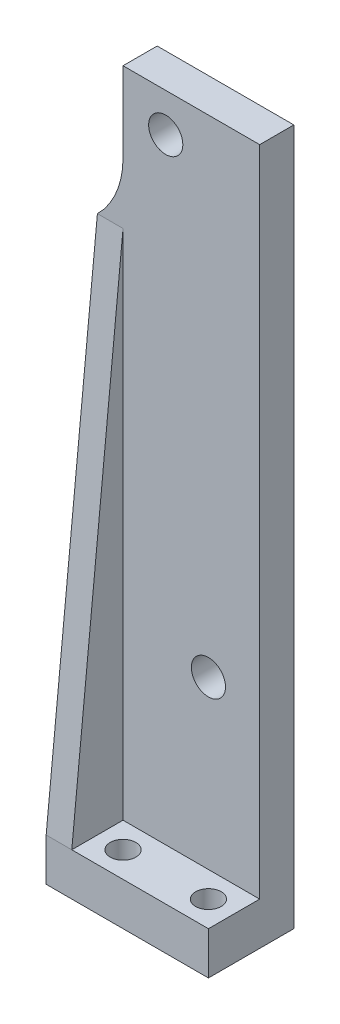
SolidWorks part; units mm, degrees
ref_plane "前视基准面" through (0, 0, 0) normal (0, 0, 1) x (1, 0, 0)
ref_plane "上视基准面" through (0, 0, 0) normal (0, 1, 0) x (1, 0, 0)
ref_plane "右视基准面" through (0, 0, 0) normal (1, 0, 0) x (0, 0, -1)
sketch "草图1" plane through (0, 0, 0) normal (0, 1, 0) x (1, 0, 0)
  line L0 (-10, 0) -> (-7, 0)
  line L1 (-10, 3) -> (6, 3)
  line L2 (-10, 3) -> (-10, -3)
  line L3 (-10, -3) -> (6, -3)
  line L4 (6, 3) -> (6, -3)
  line L5 (-10, 3) -> (6, -3) construction
  line L6 (-10, -3) -> (6, 3) construction
  line L7 (6, 0) -> (3, 0)
  circle A5 centre (-7, 0) radius 1.5
  circle A6 centre (3, 0) radius 1.5
extrude "凸台-拉伸1" add sketch "草图1" along normal blind 5 contours L7 L4 L1 L2 L0 | L0 L2 L3 L4 L7 region at (-2, 0, 0)
sketch "草图2" plane through (0, 0, -3) normal (0, 0, -1) x (-1, 0, 0)
  line L0 (-6, 0) -> (-6, 81.5)
  line L1 (-6, 81.5) -> (10, 81.5)
  line L2 (10, 81.5) -> (10, 0)
  line L3 (10, 0) -> (-6, 0)
extrude "凸台-拉伸2" add sketch "草图2" along normal blind 4 contours L0 L1 L2 L3
sketch "草图3" plane through (0, 0, -7) normal (0, 0, -1) x (-1, 0, 0)
  circle A0 centre (5, 77) radius 2
extrude "切除-拉伸1" cut sketch "草图3" against normal through all contours A0
sketch "草图4" plane through (0, 0, -7) normal (0, 0, -1) x (-1, 0, 0)
  line L0 (0, 0) -> (0, 24.5)
  circle A0 centre (0, 24.5) radius 2
extrude "切除-拉伸2" cut sketch "草图4" against normal through all contours A0
sketch "草图5" plane through (0, 0, -7) normal (0, 0, -1) x (-1, 0, 0)
  circle A0 centre (5, 77) radius 3.5
extrude "切除-拉伸3" cut sketch "草图5" against normal blind 1
sketch "草图6" plane through (-10, 0, 0) normal (-1, 0, 0) x (0, 0, 1)
  line L0 (-3, 5) -> (-3, 65)
  line L1 (-3, 81.5) -> (-3, 5) construction
  line L2 (-3, 65) -> (-7, 65)
  line L3 (-7, 81.5) -> (-7, 0) construction
  line L4 (-7, 65) -> (-7, 0)
  line L5 (-7, 0) -> (3, 0)
  line L6 (3, 0) -> (3, 5)
  line L7 (3, 5) -> (-3, 65)
  line M1 (-7, 0) -> (3, 0)
  line M2 (3, 0) -> (3, 5)
  line M3 (3, 5) -> (-3, 5)
  line M4 (-3, 5) -> (-3, 81.5)
  line M6 (-7, 81.5) -> (-7, 0)
extrude "凸台-拉伸3" add sketch "草图6" along normal blind 3 contours L2 M4 M6 M1 M2 M3 | L7 M3 M4 region at (-10, 29.3966, -4.4828) region at (-10, 25, -1)
fillet "圆角1" radius 10 1 edges at (-10, 65, -5)
